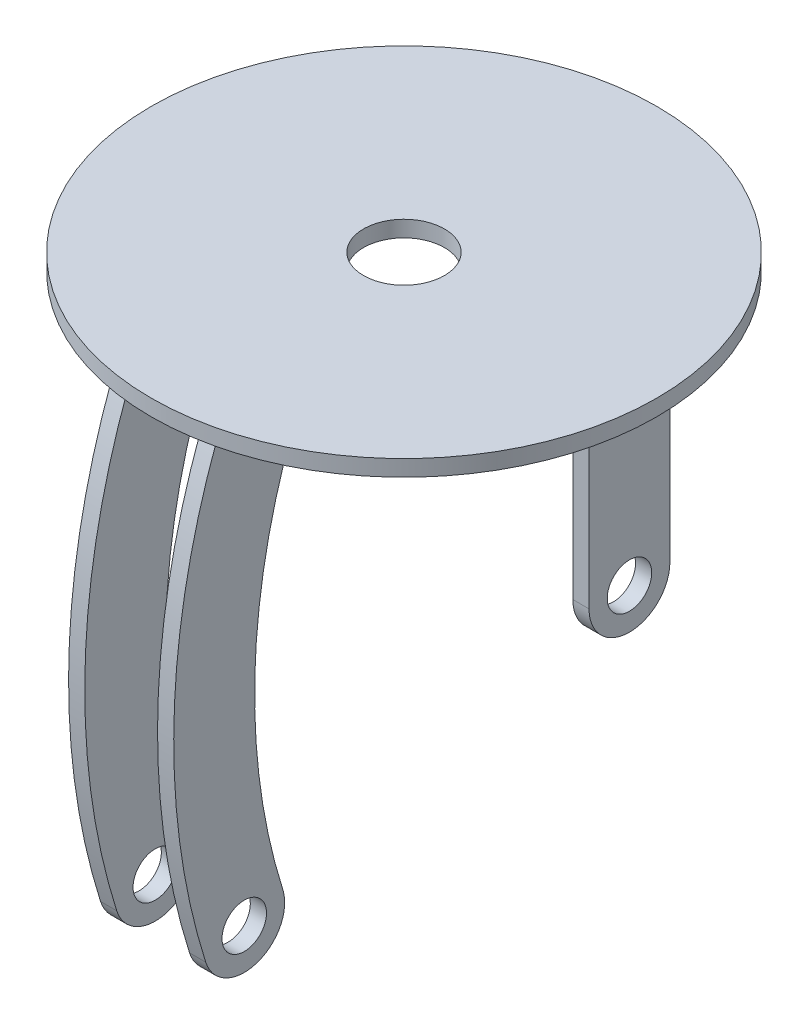
SolidWorks part; units mm, degrees
ref_plane "Front Plane" through (0, 0, 0) normal (0, 0, 1) x (1, 0, 0)
ref_plane "Top Plane" through (0, 0, 0) normal (0, 1, 0) x (1, 0, 0)
ref_plane "Right Plane" through (0, 0, 0) normal (1, 0, 0) x (0, 0, -1)
sketch "Sketch1" plane through (0, 0, 0) normal (0, 1, 0) x (1, 0, 0)
  circle A0 centre (0, 0) radius 20
  circle A1 centre (0, 0) radius 125
  dimension "D1" = 250
  dimension "D2" = 40
extrude "Boss-Extrude1" add sketch "Sketch1" along normal mid plane 8
sketch "Sketch2" plane through (0, -4, 0) normal (0, -1, 0) x (1, 0, 0)
  line L0 (-107.5, 0) -> (107.5, 0) construction
  line L1 (103.5, 20) -> (111.5, 20)
  line L2 (103.5, 20) -> (103.5, -20)
  line L3 (103.5, -20) -> (111.5, -20)
  line L4 (111.5, 20) -> (111.5, -20)
  line L5 (103.5, 20) -> (111.5, -20) construction
  line L6 (103.5, -20) -> (111.5, 20) construction
  line L7 (-111.5, 20) -> (-103.5, 20)
  line L8 (-111.5, 20) -> (-111.5, -20)
  line L9 (-111.5, -20) -> (-103.5, -20)
  line L10 (-103.5, 20) -> (-103.5, -20)
  line L11 (-111.5, 20) -> (-103.5, -20) construction
  line L12 (-111.5, -20) -> (-103.5, 20) construction
  point P0 (107.5, 0)
  point P5 (-107.5, 0)
  point P15 (0, 0)
  dimension "D1" = 8
  dimension "D2" = 215
  dimension "D3" = 40
extrude "Boss-Extrude2" add sketch "Sketch2" along normal blind 99
sketch "Sketch3" plane through (111.5, 0, 0) normal (1, 0, 0) x (0, 0, -1)
  line L1 (20, -103) -> (20, -4) construction
  line L2 (20, -103) -> (-20, -103) construction
  line L3 (-20, -103) -> (-20, -4) construction
  circle A0 centre (0, -83) radius 11
  circle A1 centre (0, -83) radius 20
  line M3 (-20, -4) -> (-20, -103)
  line M4 (-20, -103) -> (20, -103)
  line M5 (20, -103) -> (20, -4)
  dimension "D1" = 22
extrude "Cut-Extrude1" cut sketch "Sketch3" against normal through all contours A0 | A1 M4 M5 | A1 M3 M4 region at (111.5, -83, 0) region at (111.5, -98.5326, -15.5326) region at (111.5, -98.5326, 15.5326)
sketch "Sketch5" plane through (0, 0, 0) normal (1, 0, 0) x (0, 0, -1)
  line L0 (-118.5401, -4) -> (-75.4599, -4)
  line L1 (-124.07, -225.0278) -> (-85.93, -212.9722)
  line L2 (20, -4) -> (-20, -4) construction
  line L4 (-97, -4) -> (-105, -219) construction
  arc A0 (-118.5401, -4) -> (-124.07, -225.0278) centre (200.1205, -122.5557) ccw
  arc A1 (-75.4599, -4) -> (-85.93, -212.9722) centre (200.1205, -122.5557) ccw
  circle A2 centre (-105, -219) radius 20
  circle A3 centre (-105, -219) radius 11
  point P9 (-97, -4)
  dimension "D4" = 215
  dimension "D5" = 8
  dimension "D6" = 22
  dimension "D1" = 40
  dimension "D3" = 300
  dimension "D2" = 97
extrude "Boss-Extrude3" add sketch "Sketch5" along normal mid plane 8 from offset 22 contours L4 L0 A0 A2 | L0 L4 A2 A1 | L4 A2 L1 A3 | A2 L4 A3 L1 | A3 L1 A2 region at (0, -106.3802, 118.0819) region at (0, -6.1095, 86.23) region at (0, -210.7524, 115.8285) region at (0, -224.1191, 119.6378) region at (0, -207.1039, 95.9392)
extrude "Boss-Extrude4" add sketch "Sketch5<3>" along normal mid plane 8 from offset 22 contours A1 L4 A2 | L4 A2 L1 A3 | A2 L4 A3 L1 | A3 L1 A2 | L4 L0 A0 A2 region at (0, -106.3802, 118.0819) region at (0, -6.1095, 86.23) region at (0, -210.7524, 115.8285) region at (0, -224.1191, 119.6378) region at (0, -207.1039, 95.9392) offset against normal yes
sketch "Sketch5<3>" plane through (0, 0, 0) normal (1, 0, 0) x (0, 0, -1) same geometry as "Sketch5"
